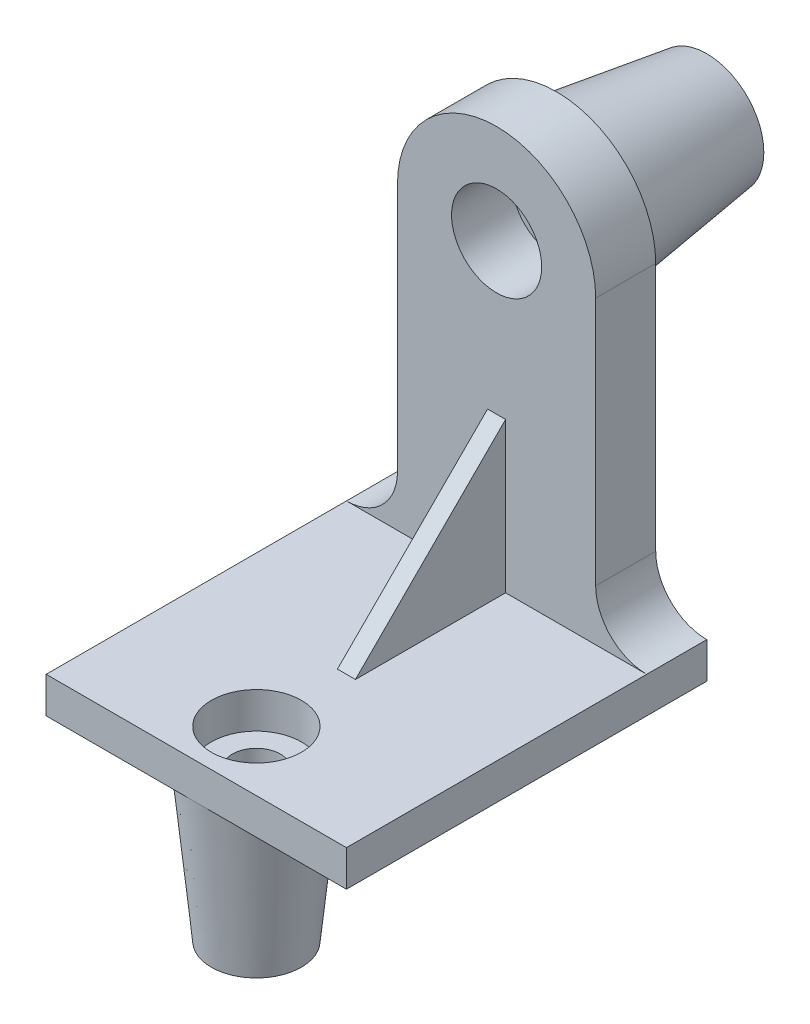
SolidWorks part; units mm, degrees
note: The reader was unsure of these and kept them because the rebuilt part matched: shared geometry of "Croquis4<7>".
ref_plane "Alzado" through (0, 0, 0) normal (0, 0, 1) x (1, 0, 0)
ref_plane "Planta" through (0, 0, 0) normal (0, 1, 0) x (1, 0, 0)
ref_plane "Vista lateral" through (0, 0, 0) normal (1, 0, 0) x (0, 0, -1)
sketch "Croquis2" plane through (0, 0, 0) normal (0, 0, 1) x (1, 0, 0)
  line L0 (0, 0) -> (0, 83)
  line L1 (0, 0) -> (-66, 0) construction
  line L2 (-83, -17) -> (17, -17)
  line L4 (-66, 0) -> (-66, 83)
  arc A1 (0, 0) -> (17, -17) centre (17, 0) ccw
  circle A2 centre (-33, 83) radius 10
  circle A3 centre (-33, 83) radius 15
  arc A4 (0, 83) -> (-66, 83) centre (-33, 83) ccw
  arc A5 (-66, 0) -> (-83, -17) centre (-83, 0) cw
  point P10 (-33, 0)
  dimension "D2" = 34
  dimension "D1" = 100
  dimension "D4" = 20
  dimension "D5" = 30
  dimension "D6" = 17
  dimension "D8" = 66
  dimension "D3" = 66
  dimension "D7" = 100
  dimension "D9" = 83
extrude "Saliente-Extruir1" add sketch "Croquis2" along normal blind 20 contours L1 L0 A4 L4 A3 | A1 L1 A5 L2
ref_plane "Plano1" through (0, 0, -50) normal (0, 0, 1) x (1, 0, 0)
sketch "Croquis4" plane through (0, 0, -50) normal (0, 0, 1) x (1, 0, 0)
  circle A0 centre (-33, 83) radius 10
  circle A1 centre (-33, 83) radius 19
  dimension "D1" = 20
  dimension "D2" = 38
sketch "Croquis5" plane through (0, 0, 0) normal (0, 0, -1) x (-1, 0, 0)
  circle A0 centre (33, 83) radius 26
  dimension "D1" = 52
loft "Recubrir2" add profiles "Croquis5" section "Croquis5" section "Croquis4" connector at (-24.95, 107.7224, 0) connector at (-26.1613, 100.7266, -50)
extrude "Cortar-Extruir1" cut sketch "Croquis4<7>" along normal up to next contours A0
sketch "Croquis4<7>" plane through (0, 0, -50) normal (0, 0, 1) x (1, 0, 0) same geometry as "Croquis4"
ref_plane "Plano2" through (0, -29, 0) normal (0, 1, 0) x (1, 0, 0)
sketch "Croquis8" plane through (0, -29, 0) normal (0, 1, 0) x (1, 0, 0)
  line L0 (17, 0) -> (-83, 0)
  line L1 (-83, 0) -> (-83, -20)
  line L2 (-83, -20) -> (17, -20)
  line L3 (17, -20) -> (17, 0)
extrude "Saliente-Extruir2" add sketch "Croquis8" along normal up to next
sketch "Croquis9" plane through (0, 0, 20) normal (0, 0, 1) x (1, 0, 0)
  line L0 (-83, -17) -> (17, -17)
  line L1 (17, -17) -> (17, -29)
  line L2 (17, -17) -> (17, -29) construction
  line L3 (17, -29) -> (-83, -29)
  line L4 (-83, -29) -> (-83, -17)
extrude "Saliente-Extruir3" add sketch "Croquis9" along normal blind 125
sketch "Croquis11" plane through (0, 0, 20) normal (0, 0, 1) x (1, 0, 0)
  line L0 (-33, -17) -> (-33, 33) construction
  line L1 (17, -17) -> (-83, -17) construction
  line L2 (-36, 33) -> (-30, 33)
  line L3 (-36, 33) -> (-36, -17)
  line L4 (-30, 33) -> (-30, -17)
  line L5 (17, -17) -> (-83, -17) construction
  line L6 (-30, -17) -> (-36, -17)
  point P7 (-33, 33)
  dimension "D1" = 50
  dimension "D2" = 6
extrude "Saliente-Extruir4" add sketch "Croquis11" along normal blind 50
sketch "Croquis12" plane through (-30, 0, 0) normal (1, 0, 0) x (0, 0, -1)
  line L0 (-70, -17) -> (-20, 33)
  line L1 (-20, 33) -> (-70, 33)
  line L2 (-70, 33) -> (-70, -17)
extrude "Cortar-Extruir2" cut sketch "Croquis12" against normal blind 50
sketch "Croquis13" plane through (0, -17, 0) normal (0, 1, 0) x (1, 0, 0)
  line L0 (-83, -20) -> (17, -20) construction
  line L1 (-33, -20) -> (-33, -100) construction
  circle A0 centre (-33, -100) radius 15
  dimension "D2" = 30
  dimension "D1" = 80
extrude "Cortar-Extruir3" cut sketch "Croquis13" against normal up to next contours A0
ref_plane "Plano4" through (0, -79, 0) normal (0, 1, 0) x (1, 0, 0)
sketch "Croquis15" plane through (0, -79, 0) normal (0, 1, 0) x (1, 0, 0)
  circle A0 centre (-33, -100) radius 15
  dimension "D1" = 30
sketch "Croquis18" plane through (0, -17, 0) normal (0, 1, 0) x (1, 0, 0)
  line L0 (17, -20) -> (17, -145) construction
  line L1 (17, -145) -> (17, -120)
  line L2 (17, -120) -> (-83, -120)
  line L3 (-83, -145) -> (-83, -20) construction
  line L4 (-83, -120) -> (-83, -145)
  line L5 (-83, -145) -> (17, -145)
  dimension "D1" = 25
extrude "Cortar-Extruir4" cut sketch "Croquis18" against normal up to next
sketch "Croquis20" plane through (0, -29, 0) normal (0, -1, 0) x (1, 0, 0)
  circle A0 centre (-33, 100) radius 20
loft "Recubrir6" add profiles "Croquis20", "Croquis15" connector at (-13.8915, -29, 94.0952) connector at (-18.8709, -79, 94.9633)
sketch "Croquis22" plane through (0, -79, 0) normal (0, -1, 0) x (1, 0, 0)
  circle A0 centre (-33, 100) radius 8
  dimension "D1" = 16
extrude "Cortar-Extruir5" cut sketch "Croquis22" against normal up to next
